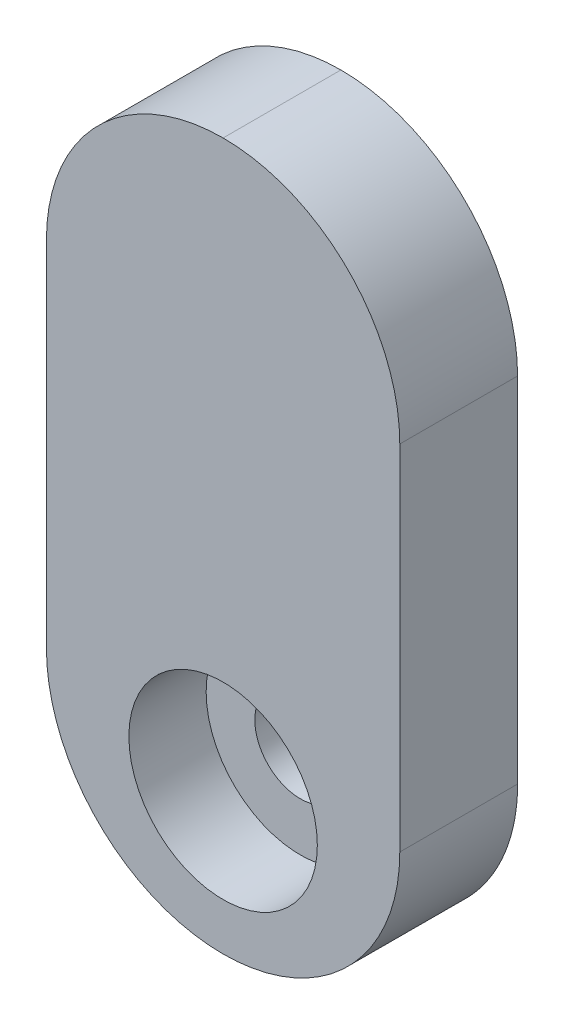
SolidWorks part; units mm, degrees
ref_plane "Front Plane" through (0, 0, 0) normal (0, 0, 1) x (1, 0, 0)
ref_plane "Top Plane" through (0, 0, 0) normal (0, 1, 0) x (1, 0, 0)
ref_plane "Right Plane" through (0, 0, 0) normal (1, 0, 0) x (0, 0, -1)
sketch "Sketch1" plane through (0, 0, 0) normal (0, 0, 1) x (1, 0, 0)
  line L1 (-9.525, 38.1) -> (9.525, 38.1)
  line L2 (-9.525, 38.1) -> (-9.525, 0)
  line L3 (-9.525, 0) -> (9.525, 0)
  line L4 (9.525, 38.1) -> (9.525, 0)
  line L5 (-9.525, 38.1) -> (9.525, 0) construction
  line L6 (-9.525, 0) -> (9.525, 38.1) construction
  point P0 (0, 19.05)
  dimension "D1" = 19.05
  dimension "D2" = 38.1
extrude "Boss-Extrude1" add sketch "Sketch1" along normal blind 6.35
hole_wizard "CBORE for #8 Socket Head Cap Screw1" positions "Sketch2" profile "Sketch3" counterbore size "#8" standard "ANSI Inch" end condition through all
sketch "Sketch2" plane through (0, 0, 6.35) normal (0, 0, 1) x (1, 0, 0)
  line L0 (-9.525, 0) -> (9.525, 0) construction
  point P0 (0, 7.62)
  dimension "D1" = 7.62
sketch "Sketch3" plane through (0, 7.62, 6.35) normal (1, 0, 0) x (0, -1, 0)
  line L0 (0, 0) -> (0, 6.35)
  line L1 (0, 6.35) -> (2.4575, 6.35)
  line L3 (2.4575, 6.35) -> (2.4575, 4.1656)
  line L4 (2.4575, 4.1656) -> (5.08, 4.1656)
  line L5 (5.08, 4.1656) -> (5.08, 0)
  line L7 (5.08, 0) -> (0, 0)
  line L11 (0, -6.35) -> (0, 107.95) construction
  dimension "Thru Hole Dia." = 4.9149
  dimension "Thru Hole Depth" = 6.35
  dimension "C'Bore Dia." = 10.16
  dimension "C'Bore Depth" = 4.1656
sketch "Sketch4" plane through (0, 0, 0) normal (0, 0, -1) x (-1, 0, 0)
  circle A0 centre (0, 7.62) radius 2.4575
  circle A1 centre (0, 7.62) radius 7.62
  circle A2 centre (0, 7.62) radius 2.4575 construction
  dimension "D1" = 15.24
extrude "Boss-Extrude2" add sketch "Sketch4" along normal blind 1.27
fillet "Fillet1" radius 9.525 4 edges at (9.525, 38.1, 3.175) (-9.525, 38.1, 3.175) (9.525, 0, 3.175) (-9.525, 0, 3.175)
